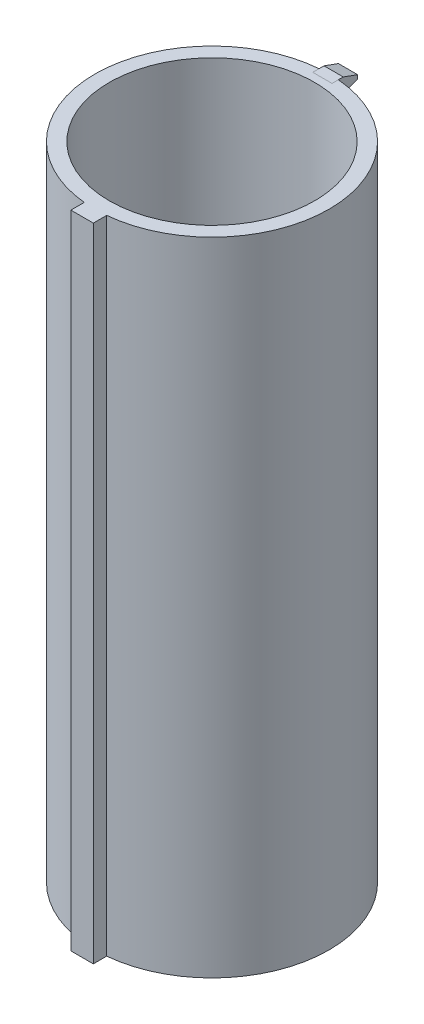
SolidWorks part; units mm, degrees
ref_plane "Спереди" through (0, 0, 0) normal (0, 0, 1) x (1, 0, 0)
ref_plane "Сверху" through (0, 0, 0) normal (0, 1, 0) x (1, 0, 0)
ref_plane "Справа" through (0, 0, 0) normal (1, 0, 0) x (0, 0, -1)
sketch "Эскиз1" plane through (0, 0, 0) normal (0, 1, 0) x (1, 0, 0)
  circle A0 centre (0, 0) radius 16
  circle A1 centre (0, 0) radius 18.25
  dimension "D1" = 32
  dimension "D2" = 36.5
extrude "Бобышка-Вытянуть1" add sketch "Эскиз1" along normal blind 100
sketch "Эскиз3" plane through (0, 0, 0) normal (1, 0, 0) x (0, 0, -1)
  line L134 (18.25, 100) -> (18.25, 0) construction
  line L269 (18.9552, 96.8584) -> (18.9552, 97.7473)
  line L270 (18.9552, 97.7473) -> (21.2052, 98.5662)
  line L271 (21.2052, 98.5662) -> (21.2052, 99.1811)
  line L272 (21.2052, 99.1811) -> (18.9552, 100)
  line L273 (18.9552, 93.7184) -> (18.9552, 94.6073)
  line L274 (18.9552, 94.6073) -> (21.2052, 95.4262)
  line L275 (21.2052, 96.0411) -> (18.9552, 96.86)
  line L276 (21.2052, 95.4262) -> (21.2052, 96.0411)
  line L277 (18.9552, 90.5784) -> (18.9552, 91.4673)
  line L278 (18.9552, 91.4673) -> (21.2052, 92.2862)
  line L279 (21.2052, 92.9011) -> (18.9552, 93.72)
  line L280 (21.2052, 92.2862) -> (21.2052, 92.9011)
  line L281 (18.9552, 87.4384) -> (18.9552, 88.3273)
  line L282 (18.9552, 88.3273) -> (21.2052, 89.1462)
  line L283 (21.2052, 89.7611) -> (18.9552, 90.58)
  line L284 (21.2052, 89.1462) -> (21.2052, 89.7611)
  line L285 (18.9552, 84.2984) -> (18.9552, 85.1873)
  line L286 (18.9552, 85.1873) -> (21.2052, 86.0062)
  line L287 (21.2052, 86.6211) -> (18.9552, 87.44)
  line L288 (21.2052, 86.0062) -> (21.2052, 86.6211)
  line L289 (18.9552, 81.1584) -> (18.9552, 82.0473)
  line L290 (18.9552, 82.0473) -> (21.2052, 82.8662)
  line L291 (21.2052, 83.4811) -> (18.9552, 84.3)
  line L292 (21.2052, 82.8662) -> (21.2052, 83.4811)
  line L293 (18.9552, 78.0184) -> (18.9552, 78.9073)
  line L294 (18.9552, 78.9073) -> (21.2052, 79.7262)
  line L295 (21.2052, 80.3411) -> (18.9552, 81.16)
  line L296 (21.2052, 79.7262) -> (21.2052, 80.3411)
  line L297 (18.9552, 74.8784) -> (18.9552, 75.7673)
  line L298 (18.9552, 75.7673) -> (21.2052, 76.5862)
  line L299 (21.2052, 77.2011) -> (18.9552, 78.02)
  line L300 (21.2052, 76.5862) -> (21.2052, 77.2011)
  line L301 (18.9552, 71.7384) -> (18.9552, 72.6273)
  line L302 (18.9552, 72.6273) -> (21.2052, 73.4462)
  line L303 (21.2052, 74.0611) -> (18.9552, 74.88)
  line L304 (21.2052, 73.4462) -> (21.2052, 74.0611)
  line L305 (18.9552, 68.5984) -> (18.9552, 69.4873)
  line L306 (18.9552, 69.4873) -> (21.2052, 70.3062)
  line L307 (21.2052, 70.9211) -> (18.9552, 71.74)
  line L308 (21.2052, 70.3062) -> (21.2052, 70.9211)
  line L309 (18.9552, 65.4584) -> (18.9552, 66.3473)
  line L310 (18.9552, 66.3473) -> (21.2052, 67.1662)
  line L311 (21.2052, 67.7811) -> (18.9552, 68.6)
  line L312 (21.2052, 67.1662) -> (21.2052, 67.7811)
  line L313 (18.9552, 62.3184) -> (18.9552, 63.2073)
  line L314 (18.9552, 63.2073) -> (21.2052, 64.0262)
  line L315 (21.2052, 64.6411) -> (18.9552, 65.46)
  line L316 (21.2052, 64.0262) -> (21.2052, 64.6411)
  line L317 (18.9552, 59.1784) -> (18.9552, 60.0673)
  line L318 (18.9552, 60.0673) -> (21.2052, 60.8862)
  line L319 (21.2052, 61.5011) -> (18.9552, 62.32)
  line L320 (21.2052, 60.8862) -> (21.2052, 61.5011)
  line L321 (18.9552, 56.0384) -> (18.9552, 56.9273)
  line L322 (18.9552, 56.9273) -> (21.2052, 57.7462)
  line L323 (21.2052, 58.3611) -> (18.9552, 59.18)
  line L324 (21.2052, 57.7462) -> (21.2052, 58.3611)
  line L325 (18.9552, 52.8984) -> (18.9552, 53.7873)
  line L326 (18.9552, 53.7873) -> (21.2052, 54.6062)
  line L327 (21.2052, 55.2211) -> (18.9552, 56.04)
  line L328 (21.2052, 54.6062) -> (21.2052, 55.2211)
  line L329 (18.9552, 49.7584) -> (18.9552, 50.6473)
  line L330 (18.9552, 50.6473) -> (21.2052, 51.4662)
  line L331 (21.2052, 52.0811) -> (18.9552, 52.9)
  line L332 (21.2052, 51.4662) -> (21.2052, 52.0811)
  line L333 (18.9552, 46.6184) -> (18.9552, 47.5073)
  line L334 (18.9552, 47.5073) -> (21.2052, 48.3262)
  line L335 (21.2052, 48.9411) -> (18.9552, 49.76)
  line L336 (21.2052, 48.3262) -> (21.2052, 48.9411)
  line L337 (18.9552, 43.4784) -> (18.9552, 44.3673)
  line L338 (18.9552, 44.3673) -> (21.2052, 45.1862)
  line L339 (21.2052, 45.8011) -> (18.9552, 46.62)
  line L340 (21.2052, 45.1862) -> (21.2052, 45.8011)
  line L341 (18.9552, 40.3384) -> (18.9552, 41.2273)
  line L342 (18.9552, 41.2273) -> (21.2052, 42.0462)
  line L343 (21.2052, 42.6611) -> (18.9552, 43.48)
  line L437 (18.9552, 100) -> (17.2052, 100)
  line L438 (17.2052, 100) -> (17.2052, 0)
  line L439 (21.2052, 42.0462) -> (21.2052, 42.6611)
  line L440 (18.9552, 37.1984) -> (18.9552, 38.0873)
  line L441 (18.9552, 38.0873) -> (21.2052, 38.9062)
  line L442 (21.2052, 39.5211) -> (18.9552, 40.34)
  line L443 (21.2052, 38.9062) -> (21.2052, 39.5211)
  line L444 (18.9552, 34.0584) -> (18.9552, 34.9473)
  line L445 (18.9552, 34.9473) -> (21.2052, 35.7662)
  line L446 (21.2052, 36.3811) -> (18.9552, 37.2)
  line L447 (21.2052, 35.7662) -> (21.2052, 36.3811)
  line L448 (18.9552, 30.9184) -> (18.9552, 31.8073)
  line L449 (18.9552, 31.8073) -> (21.2052, 32.6262)
  line L450 (21.2052, 33.2411) -> (18.9552, 34.06)
  line L451 (21.2052, 32.6262) -> (21.2052, 33.2411)
  line L452 (18.9552, 27.7784) -> (18.9552, 28.6673)
  line L453 (18.9552, 28.6673) -> (21.2052, 29.4862)
  line L454 (21.2052, 30.1011) -> (18.9552, 30.92)
  line L455 (21.2052, 29.4862) -> (21.2052, 30.1011)
  line L456 (18.9552, 24.6384) -> (18.9552, 25.5273)
  line L457 (18.9552, 25.5273) -> (21.2052, 26.3462)
  line L458 (21.2052, 26.9611) -> (18.9552, 27.78)
  line L459 (21.2052, 26.3462) -> (21.2052, 26.9611)
  line L460 (18.9552, 21.4984) -> (18.9552, 22.3873)
  line L461 (18.9552, 22.3873) -> (21.2052, 23.2062)
  line L462 (21.2052, 23.8211) -> (18.9552, 24.64)
  line L463 (21.2052, 23.2062) -> (21.2052, 23.8211)
  line L464 (18.9552, 18.3584) -> (18.9552, 19.2473)
  line L465 (18.9552, 19.2473) -> (21.2052, 20.0662)
  line L466 (21.2052, 20.6811) -> (18.9552, 21.5)
  line L467 (21.2052, 20.0662) -> (21.2052, 20.6811)
  line L468 (18.9552, 15.2184) -> (18.9552, 16.1073)
  line L469 (18.9552, 16.1073) -> (21.2052, 16.9262)
  line L470 (21.2052, 17.5411) -> (18.9552, 18.36)
  line L471 (21.2052, 16.9262) -> (21.2052, 17.5411)
  line L472 (18.9552, 12.0784) -> (18.9552, 12.9673)
  line L473 (18.9552, 12.9673) -> (21.2052, 13.7862)
  line L474 (21.2052, 14.4011) -> (18.9552, 15.22)
  line L475 (21.2052, 13.7862) -> (21.2052, 14.4011)
  line L476 (18.9552, 8.9384) -> (18.9552, 9.8273)
  line L477 (18.9552, 9.8273) -> (21.2052, 10.6462)
  line L478 (21.2052, 11.2611) -> (18.9552, 12.08)
  line L479 (21.2052, 10.6462) -> (21.2052, 11.2611)
  line L480 (18.9552, 5.7984) -> (18.9552, 6.6873)
  line L481 (18.9552, 6.6873) -> (21.2052, 7.5062)
  line L482 (21.2052, 8.1211) -> (18.9552, 8.94)
  line L483 (21.2052, 7.5062) -> (21.2052, 8.1211)
  line L484 (18.9552, 2.6584) -> (18.9552, 3.5473)
  line L485 (18.9552, 3.5473) -> (21.2052, 4.3662)
  line L486 (21.2052, 4.9811) -> (18.9552, 5.8)
  line L487 (21.2052, 4.3662) -> (21.2052, 4.9811)
  line L488 (18.9552, 2.6584) -> (18.9552, 0)
  line L489 (18.9552, 0) -> (17.2052, 0)
  line L490 (-18.25, 0) -> (18.25, 0) construction
  line L491 (21.2052, 98.8736) -> (18.25, 98.8736) construction
  point P8 (0, 0)
  point P162 (21.2052, 99.1811)
  dimension "D1" = 31
  dimension "D2" = 40
  dimension "D3" = 2.9552
  dimension "D4" = 0.7052
  dimension "D5" = 3.1416
  dimension "D6" = 0.6149
  dimension "D7" = 1.1264
extrude "Бобышка-Вытянуть2" add sketch "Эскиз3" along normal blind 1.5 and the other way blind 1.5 contours L489 L488 L484 L485 L487 L486 L480 L481 L483 L482 L476 L477 L479 L478 L472 L473 L475 L474 L468 L469 L471 L470 L464 L465 L467 L466 L460 L461 L463 L462 L456 L457 L459 L458 L452 region at (0, 50.645, -18.7296)
sketch "Эскиз5" plane through (0, 0, 0) normal (0, -1, 0) x (1, 0, 0)
  line L0 (0, 0) -> (0, 18.25) construction
  line L2 (-1.75, 20.25) -> (1.75, 20.25)
  line L3 (-1.75, 20.25) -> (-1.75, 16.25)
  line L4 (-1.75, 16.25) -> (1.75, 16.25)
  line L5 (1.75, 20.25) -> (1.75, 16.25)
  line L6 (-1.75, 20.25) -> (1.75, 16.25) construction
  line L7 (-1.75, 16.25) -> (1.75, 20.25) construction
  circle A0 centre (0, 0) radius 18.25 construction
  arc A1 (1.5, -18.1883) -> (-1.5, -18.1883) centre (0, 0) ccw construction
  point P7 (0, 18.25)
  point P8 (0, 18.25)
  point P11 (0, -18.25)
  point P12 (0, 0)
  point P13 (0, 0)
  point P14 (0, 0)
  point P15 (0, -18.25)
  point P16 (0, 0)
  point P17 (0, 18.25)
  dimension "D1" = 3.5
  dimension "D2" = 2
sketch "Эскиз4" plane through (0, 100, 0) normal (0, 1, 0) x (1, 0, 0)
  line L0 (1.5, 21.2052) -> (1.5, 17.2052)
  line L1 (1.5, 17.2052) -> (-1.5, 17.2052)
  line L2 (-1.5, 17.2052) -> (-1.5, 21.2052)
  line L3 (1.5, 21.2052) -> (1.5, 18.9552) construction
  line L4 (-1.5, 21.2052) -> (-1.5, 18.9552) construction
  line L5 (-1.5, 21.2052) -> (1.5, 21.2052) construction
  point P5 (1.5, 20.4)
  point P8 (0, 0)
  point P9 (1.5365, 20.2959)
  point P10 (1.5, 20.4)
  point P13 (-1.5, 20.4)
  point P14 (0, 0)
  point P15 (-1.5, 20.4)
  point P18 (1.5, 20.4)
  point P19 (1.5, 21.1689)
  point P20 (1.5, 21.2052)
  point P22 (-1.5, 21.2052)
  dimension "D1" = 4
extrude "Бобышка-Вытянуть4" add sketch "Эскиз5" against normal up to surface (100 mm away) up to face at (0, 100, -9.4622)
split "Разделить2" trim tools "Эскиз4" bodies to split 108 resulting bodies 109 110
